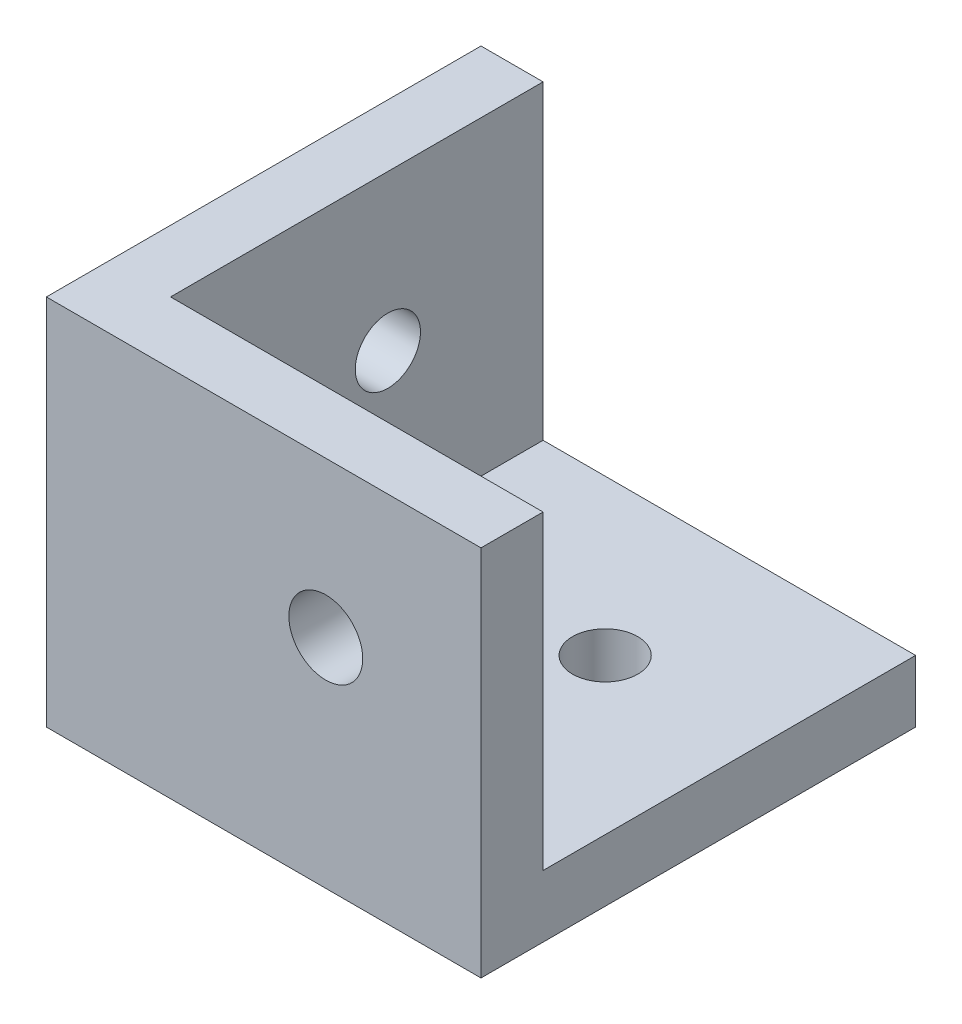
SolidWorks part; units mm, degrees
ref_plane "前视基准面" through (0, 0, 0) normal (0, 0, 1) x (1, 0, 0)
ref_plane "上视基准面" through (0, 0, 0) normal (0, 1, 0) x (1, 0, 0)
ref_plane "右视基准面" through (0, 0, 0) normal (1, 0, 0) x (0, 0, -1)
other "Configuration Table"
sketch "草图1" plane through (0, 0, 0) normal (0, 1, 0) x (1, 0, 0)
  line L1 (-12, 12) -> (12, 12)
  line L2 (-12, 12) -> (-12, -12)
  line L3 (-12, -12) -> (12, -12)
  line L4 (12, 12) -> (12, -12)
  line L5 (-12, 12) -> (12, -12) construction
  line L6 (-12, -12) -> (12, 12) construction
  line L7 (12, 12) -> (-16, 12)
  line L8 (12, 12) -> (12, -16)
  line L9 (12, -16) -> (-16, -16)
  line L10 (-16, 12) -> (-16, -16)
  circle A0 centre (2, 2) radius 2.1
  point P0 (0, 0)
  dimension "D6" = 4.2
  dimension "D1" = 24
  dimension "D2" = 24
  dimension "D3" = 4
  dimension "D4" = 4
  dimension "D5" = 10
extrude "凸台-拉伸1" add sketch "草图1" along normal blind 4 contours L4 L1 L2 L3 A0 region at (-0.0493, 0, 0.0493)
extrude "凸台-拉伸2" add sketch "草图1<3>" along normal blind 24 contours L7 L10 L9 L8 L3 L2 region at (-12.396, 0, 0)
sketch "草图1<3>" plane through (0, 0, 0) normal (0, 1, 0) x (1, 0, 0) same geometry as "草图1"
sketch "草图2" plane through (0, 0, 16) normal (0, 0, 1) x (1, 0, 0)
  line L0 (12, 0) -> (-16, 0) construction
  line L1 (12, 24) -> (12, 0) construction
  circle A0 centre (2, 14) radius 2.3799
  dimension "D1" = 14
  dimension "D2" = 10
extrude "切除-拉伸1" cut sketch "草图2" against normal through all
sketch "草图3" plane through (-16, 0, 0) normal (-1, 0, 0) x (0, 0, 1)
  line L0 (-12, 0) -> (16, 0) construction
  line L1 (-12, 24) -> (-12, 0) construction
  circle A0 centre (-2, 14) radius 2.1
  dimension "D1" = 4.2
  dimension "D2" = 14
  dimension "D3" = 10
extrude "切除-拉伸2" cut sketch "草图3" against normal through all contours A0
